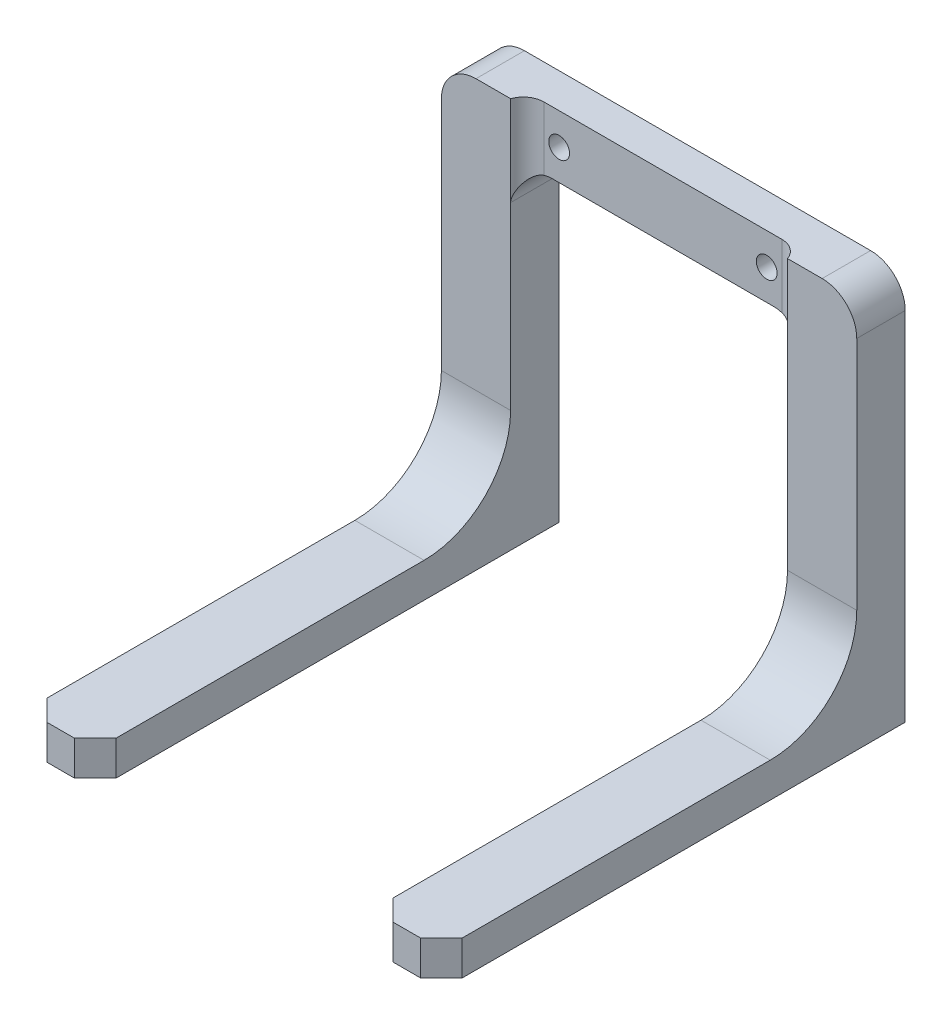
SolidWorks part; units mm, degrees
ref_plane "Front Plane" through (0, 0, 0) normal (0, 0, 1) x (1, 0, 0)
ref_plane "Top Plane" through (0, 0, 0) normal (0, 1, 0) x (1, 0, 0)
ref_plane "Right Plane" through (0, 0, 0) normal (1, 0, 0) x (0, 0, -1)
sketch "Sketch1" plane through (0, 0, 0) normal (0, 1, 0) x (1, 0, 0)
  line L1 (-30, 3.5) -> (30, 3.5)
  line L2 (-30, 3.5) -> (-30, -3.5)
  line L3 (-30, -3.5) -> (30, -3.5)
  line L4 (30, 3.5) -> (30, -3.5)
  line L5 (-30, 3.5) -> (30, -3.5) construction
  line L6 (-30, -3.5) -> (30, 3.5) construction
  point P0 (0, 0)
  dimension "D1" = 60
  dimension "D2" = 7
extrude "Boss-Extrude1" add sketch "Sketch1" along normal blind 9
sketch "Sketch2" plane through (0, 0, 3.5) normal (0, 0, 1) x (1, 0, 0)
  line L0 (-30, 9) -> (30, 9) construction
  line L1 (-20, 9) -> (20, 9)
  line L2 (-20, 9) -> (-20, 0)
  line L3 (-20, 0) -> (20, 0)
  line L4 (20, 9) -> (20, 0)
  line L5 (-30, 0) -> (30, 0) construction
  line L6 (-30, 9) -> (-30, 0) construction
  line L7 (30, 9) -> (30, 0) construction
  dimension "D1" = 10
  dimension "D2" = 10
extrude "Cut-Extrude1" cut sketch "Sketch2" against normal blind 2
fillet "Fillet2" radius 3 2 edges at (-20, 4.5, 1.5) (20, 4.5, 1.5)
fillet "Fillet3" radius 5 2 edges at (30, 9, 0) (-30, 9, 0)
sketch "Sketch3" plane through (0, 0, 0) normal (0, -1, 0) x (1, 0, 0)
  line L1 (-20, 3.5) -> (-30, 3.5)
  line L2 (-20, 3.5) -> (-20, -3.5)
  line L3 (-20, -3.5) -> (-30, -3.5)
  line L4 (-30, 3.5) -> (-30, -3.5)
  line L5 (20, 3.5) -> (30, 3.5)
  line L6 (20, 3.5) -> (20, -3.5)
  line L7 (20, -3.5) -> (30, -3.5)
  line L8 (30, 3.5) -> (30, -3.5)
extrude "Boss-Extrude2" add sketch "Sketch3" along normal blind 47.5
fillet "Fillet5" radius 4 2 edges at (20, 0, 0) (-20, 0, 0)
sketch "Sketch4" plane through (0, 0, 3.5) normal (0, 0, 1) x (1, 0, 0)
  line L0 (-20, -47.5) -> (-20, -4) construction
  line L1 (-30, -47.5) -> (-20, -47.5)
  line L2 (-30, -47.5) -> (-30, -42.5)
  line L3 (-30, -42.5) -> (-20, -42.5)
  line L4 (-20, -47.5) -> (-20, -42.5)
  dimension "D1" = 5
extrude "Boss-Extrude3" add sketch "Sketch4" along normal blind 60
sketch "Sketch5" plane through (0, 0, 3.5) normal (0, 0, 1) x (1, 0, 0)
  line L0 (30, 4) -> (30, -47.5) construction
  line L1 (20, -47.5) -> (30, -47.5)
  line L2 (20, -47.5) -> (20, -42.5)
  line L3 (20, -42.5) -> (30, -42.5)
  line L4 (30, -47.5) -> (30, -42.5)
  dimension "D1" = 5
extrude "Boss-Extrude4" add sketch "Sketch5" along normal blind 60
fillet "Fillet7" radius 12.5 2 edges at (25, -42.5, 3.5) (-25, -42.5, 3.5)
chamfer "Chamfer2" distance 3 angle 45 4 edges at (30, -45, 63.5) (20, -45, 63.5) (-20, -45, 63.5) (-30, -45, 63.5)
sketch "Sketch6" plane through (0, 0, -3.5) normal (0, 0, -1) x (-1, 0, 0)
  line L0 (-17.1716, -0.1754) -> (-30, -0.1754) construction
  line L1 (-30, 4) -> (-30, -47.5) construction
  line L2 (16, 0) -> (30, 0) construction
  line L3 (30, 4) -> (30, -47.5) construction
  line L4 (-30, 2.3246) -> (30, 2.3246) construction
  line L5 (-29.3301, 6.5) -> (29.3301, 6.5) construction
  line L6 (-25, 9) -> (25, 9) construction
  line L7 (0, 2.3246) -> (0, 6.5) construction
  line L8 (0, 4.4123) -> (29.983, 4.4123) construction
  line L9 (0, 4.4123) -> (-29.983, 4.4123) construction
  arc A0 (-25, 9) -> (-30, 4) centre (-25, 4) ccw construction
  arc A1 (30, 4) -> (25, 9) centre (25, 4) ccw construction
  circle A2 centre (-14.9915, 4.4123) radius 1.5
  circle A3 centre (14.9915, 4.4123) radius 1.5
  dimension "D1" = 2.5
  dimension "D2" = 2.5
extrude "Cut-Extrude2" cut sketch "Sketch6" against normal blind 10
